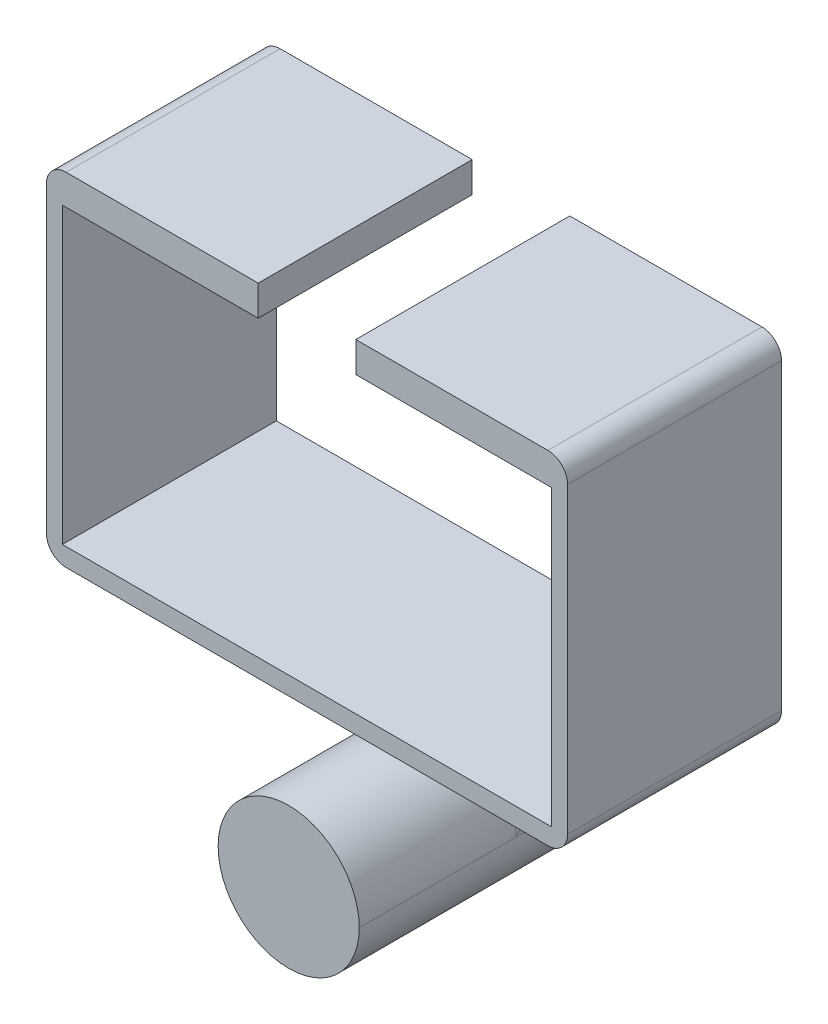
SolidWorks part; units mm, degrees
material "ASTM A36 Steel"
ref_plane "Front Plane" through (0, 0, 0) normal (0, 0, 1) x (1, 0, 0)
ref_plane "Top Plane" through (0, 0, 0) normal (0, 1, 0) x (1, 0, 0)
ref_plane "Right Plane" through (0, 0, 0) normal (1, 0, 0) x (0, 0, -1)
sketch "Sketch1" plane through (0, 0, 0) normal (0, 0, 1) x (1, 0, 0)
  line L12 (-33.7617, 0) -> (33.7617, 0)
  line L13 (-33.7617, 0) -> (-33.7617, 44.3635)
  line L14 (-33.7617, 44.3635) -> (-6.3246, 44.3635)
  line L15 (-6.3246, 44.3635) -> (-6.3246, 40.4265)
  line L16 (-6.3246, 40.4265) -> (-31.7043, 40.4265)
  line L17 (-31.7043, 40.4265) -> (-31.7043, 2.3519)
  line L18 (-31.7043, 2.3519) -> (31.7043, 2.3519)
  line L19 (31.7043, 2.3519) -> (31.7043, 40.4265)
  line L20 (31.7043, 40.4265) -> (6.3246, 40.4265)
  line L21 (6.3246, 40.4265) -> (6.3246, 44.3635)
  line L22 (6.3246, 44.3635) -> (33.7617, 44.3635)
  line L23 (33.7617, 44.3635) -> (33.7617, 0)
  point P3 (0, 0)
  dimension "D4" = 3.937
  dimension "D5" = 2.0574
  dimension "D6" = 2.0574
  dimension "D2" = 2.3519
  dimension "D7" = 38.0746
extrude "Boss-Extrude1" add sketch "Sketch1" along normal blind 27.7315
sketch "Sketch2" plane through (0, 0, 0) normal (0, 0, 1) x (1, 0, 0)
  line L5 (-9.144, 0) -> (9.144, 0)
  line L6 (-9.144, 0) -> (-9.144, -19.05)
  line L7 (9.144, 0) -> (9.144, -19.05)
  arc A1 (-9.144, -19.05) -> (9.144, -19.05) centre (0, -19.05) ccw
  point P2 (0, 0)
  dimension "D3" = 9.144
  dimension "D1" = 18.288
  dimension "D2" = 19.05
extrude "Boss-Extrude2" add sketch "Sketch2" along normal blind 4.7037
sketch "Sketch4" plane through (0, 0, 4.7037) normal (0, 0, 1) x (1, 0, 0)
  circle A2 centre (0, -19.05) radius 9.144
  arc A3 (-9.144, -19.05) -> (9.144, -19.05) centre (0, -19.05) ccw construction
extrude "Boss-Extrude3" add sketch "Sketch4" along normal blind 25.4
sketch "Sketch5" plane through (0, 0, 0) normal (0, 0, 1) x (1, 0, 0)
  line L0 (-9.144, -19.05) -> (9.144, -19.05)
  arc A0 (9.144, -19.05) -> (-9.144, -19.05) centre (0, -19.05) ccw
split line "Split Line1"
fillet "Fillet1" radius 2.54 4 edges at (-33.7617, 44.3635, 13.8658) (33.7617, 44.3635, 13.8658) (33.7617, 0, 13.8658) (-33.7617, 0, 13.8658)
fillet "Fillet2" radius 5.08 1 edges at (0, -9.906, 4.7037)
fillet "Fillet3" radius 3.81 3 edges at (-9.144, 0, 2.3519) (0, 0, 4.7037) (9.144, 0, 2.3519)
equation "\"a\"= 0.498"
equation "\"b\"= 0.9992"
equation "\"c\"= 1.499"
equation "\"Overall Width\"= \"a\" + \"b\" + \"b\""
equation "\"Pin Diameter\"= 0.72"
equation "\"Hanger Width\"= 0.72"
equation "\"Wall Width\"= 0.081"
equation "\"Pin Length\"= 1"
equation "\"Flange Width\"= 0.155"
equation "\"Flange Length\"= 600 / ( 2 * 0.36 * 9000 )"
equation "\"Bracket Width\"= \"b\" + \"Flange Length\""
equation "\"D1@Boss-Extrude1\"=\"Bracket Width\""
equation "\"D1@Boss-Extrude2\"=\"Flange Length\" * 2"
equation "\"D1@Boss-Extrude3\"=\"Pin Length\""
equation "\"D1@Sketch2\"=\"Hanger Width\""
equation "\"Pin to Base\"= 0.75"
equation "\"D2@Sketch2\"=\"Pin to Base\""
equation "\"D4@Sketch1\"=\"Flange Width\""
equation "\"D2@Sketch1\"=\"Flange Length\""
equation "\"Flange Height\"= 0.0876"
equation "\"D1@Sketch1\"=\"Overall Width\""
equation "\"D7@Sketch1\"=\"c\""
equation "\"D3@Sketch1\"=\"b\""
equation "\"D6@Sketch1\"=\"Wall Width\""
equation "\"D5@Sketch1\"=\"Wall Width\""
